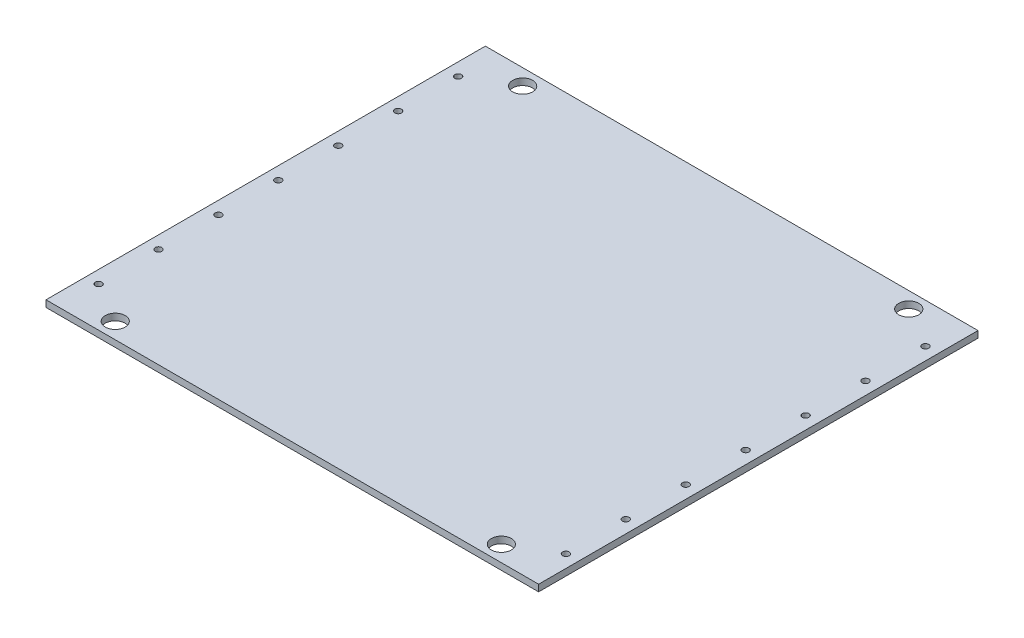
SolidWorks part; units mm, degrees
ref_plane "前视基准面" through (0, 0, 0) normal (0, 0, 1) x (1, 0, 0)
ref_plane "上视基准面" through (0, 0, 0) normal (0, 1, 0) x (1, 0, 0)
ref_plane "右视基准面" through (0, 0, 0) normal (1, 0, 0) x (0, 0, -1)
other "Configuration Table"
sketch "草图1" plane through (0, 0, 0) normal (0, 1, 0) x (1, 0, 0)
  line L1 (185, -165) -> (-185, -165)
  line L2 (185, -165) -> (185, 165)
  line L3 (185, 165) -> (-185, 165)
  line L4 (-185, -165) -> (-185, 165)
  line L5 (185, -165) -> (-185, 165) construction
  line L6 (185, 165) -> (-185, -165) construction
  point P0 (0, 0)
  dimension "D1" = 370
  dimension "D2" = 330
extrude "凸台-拉伸1" add sketch "草图1" along normal blind 5
sketch "草图2" plane through (0, 5, 0) normal (0, 1, 0) x (1, 0, 0)
  circle A0 centre (-159.5, 159) radius 1.6
  circle A1 centre (-128.5, 159) radius 1.6
  circle A2 centre (-159.5, 128) radius 1.6022
  circle A3 centre (-128.5, 128) radius 1.6
  circle A4 centre (128.5, 159) radius 1.6
  circle A5 centre (159.5, 159) radius 1.6
  circle A6 centre (128.5, 128) radius 1.6
  circle A7 centre (159.5, 128) radius 1.6
  circle A8 centre (128.5, -128) radius 1.6
  circle A9 centre (159.5, -128) radius 1.6
  circle A10 centre (159.5, -159) radius 1.6
  circle A11 centre (128.5, -159) radius 1.6
  circle A12 centre (-128.5, -159) radius 1.6
  circle A13 centre (-159.5, -159) radius 1.6
  circle A14 centre (-159.5, -128) radius 1.6
  circle A15 centre (-128.5, -128) radius 1.6
sketch "草图3" plane through (0, 5, 0) normal (0, 1, 0) x (1, 0, 0)
  line L0 (-110, 60) -> (-110, 40)
  line L1 (110, -110) -> (-110, -110) construction
  line L2 (110, -110) -> (110, 110) construction
  line L3 (110, 110) -> (-110, 110) construction
  line L4 (-110, -110) -> (-110, 110) construction
  line L5 (110, -110) -> (-110, 110) construction
  line L6 (110, 110) -> (-110, -110) construction
  line L7 (-110, 110) -> (110, 110)
  line L8 (-110, 110) -> (-110, 90)
  line L9 (-110, 90) -> (110, 90)
  line L10 (110, 110) -> (110, 90)
  line L11 (-110, 60) -> (110, 60)
  line L12 (110, 60) -> (110, 40)
  line L13 (-110, 40) -> (110, 40)
  line L14 (-110, 10) -> (-110, -10)
  line L15 (-110, 10) -> (110, 10)
  line L16 (110, 10) -> (110, -10)
  line L17 (-110, -10) -> (110, -10)
  line L18 (-110, -40) -> (-110, -60)
  line L19 (-110, -40) -> (110, -40)
  line L20 (110, -40) -> (110, -60)
  line L21 (-110, -60) -> (110, -60)
  line L22 (-110, -90) -> (-110, -110)
  line L23 (-110, -90) -> (110, -90)
  line L24 (110, -90) -> (110, -110)
  line L25 (-110, -110) -> (110, -110)
  point P0 (0, 0)
  dimension "D1" = 220
  dimension "D2" = 220
  dimension "D3" = 20
  dimension "D4" = 5
extrude "切除-拉伸2" cut sketch "草图3" against normal through all contours L10 L7 L8 L9 | L0 L13 L12 L11 | L14 L17 L16 L15 | L18 L21 L20 L19 | L22 L25 L24 L23 | L8 L7 L10 L9 | L0 L13 L12 L11 region at (0, 5, -50) region at (0, 5, -100) region at (0, 5, 0) region at (0, 5, 50) region at (0, 5, 100)
sketch "草图8" plane through (0, 5, 0) normal (0, 1, 0) x (1, 0, 0)
  line L0 (120, 0) -> (-120, 0)
  line L1 (0, -120) -> (0, 120)
  point P4 (0, 0)
  point P8 (0, 0)
sketch "草图9" plane through (0, 5, 0) normal (0, 1, 0) x (1, 0, 0)
  line L1 (-117.6798, 117.0824) -> (121.8613, 117.0824)
  line L2 (-117.6798, 117.0824) -> (-117.6798, -116.4851)
  line L3 (-117.6798, -116.4851) -> (121.8613, -116.4851)
  line L4 (121.8613, 117.0824) -> (121.8613, -116.4851)
extrude "凸台-拉伸2" add sketch "草图9" against normal blind 5
sketch "草图12" plane through (0, 5, 0) normal (0, 1, 0) x (1, 0, 0)
  line L0 (185, 0) -> (175.5, 0) construction
  line L1 (185, -165) -> (185, 165) construction
  line L2 (0, -120) -> (0, 120) construction
  line L3 (120, 0) -> (-120, 0) construction
  line L4 (0, -120) -> (0, 120)
  line L5 (120, 0) -> (-120, 0)
  line L6 (-185, 0) -> (-175.5, 0) construction
  circle A0 centre (175.5, 0) radius 2.5
  circle A1 centre (175.5, 45) radius 2.5
  circle A2 centre (175.5, 90) radius 2.5
  circle A3 centre (175.5, 135) radius 2.5
  circle A4 centre (175.5, -135) radius 2.5
  circle A5 centre (175.5, -90) radius 2.5
  circle A6 centre (175.5, -45) radius 2.5
  circle A7 centre (-175.5, -45) radius 2.5
  circle A8 centre (-175.5, -90) radius 2.5
  circle A9 centre (-175.5, -135) radius 2.5
  circle A10 centre (-175.5, 135) radius 2.5
  circle A11 centre (-175.5, 90) radius 2.5
  circle A12 centre (-175.5, 45) radius 2.5
  circle A13 centre (-175.5, 0) radius 2.5
  dimension "D2" = 5
  dimension "D1" = 9.5
  dimension "D3" = 4
extrude "切除-拉伸6" cut sketch "草图12" against normal blind 10 contours A9 | A8 | A7 | A13 | A12 | A11 | A10 | A4 | A5 | A6 | A0 | A1 | A2 | A3 region at (175.5, 5, 0) region at (175.5, 5, -45) region at (175.5, 5, -90) region at (175.5, 5, -135) region at (175.5, 5, 135) region at (175.5, 5, 90) region at (175.5, 5, 45) region at (-175.5, 5, 45) region at (-175.5, 5, 90) region at (-175.5, 5, 135) region at (-175.5, 5, -135) region at (-175.5, 5, -90) region at (-175.5, 5, -45) region at (-175.5, 5, 0)
sketch "草图13" plane through (0, 5, 0) normal (0, 1, 0) x (1, 0, 0)
  line L0 (120, 0) -> (-120, 0) construction
  line L1 (-185, -165) -> (-145, -165)
  line L2 (-185, -165) -> (-185, -153)
  line L3 (-185, -153) -> (-145, -153)
  line L4 (-145, -165) -> (-145, -153)
  line L5 (0, -120) -> (0, 120) construction
  line L6 (120, 0) -> (-120, 0)
  line L7 (0, -120) -> (0, 120)
  circle A1 centre (-145, -153) radius 7.5
  circle A2 centre (145, -153) radius 7.5
  circle A3 centre (145, 153) radius 7.5
  circle A4 centre (-145, 153) radius 7.5
  dimension "D3" = 15
  dimension "D1" = 40
  dimension "D2" = 12
extrude "切除-拉伸7" cut sketch "草图13" against normal blind 10 contours A2 | L4 A1 L3 | L3 A1 L4 | A4 | A3 region at (-148.1831, 5, 156.1831) region at (-143.939, 5, 151.939) region at (145, 5, 153) region at (145, 5, -153) region at (-145, 5, -153)
